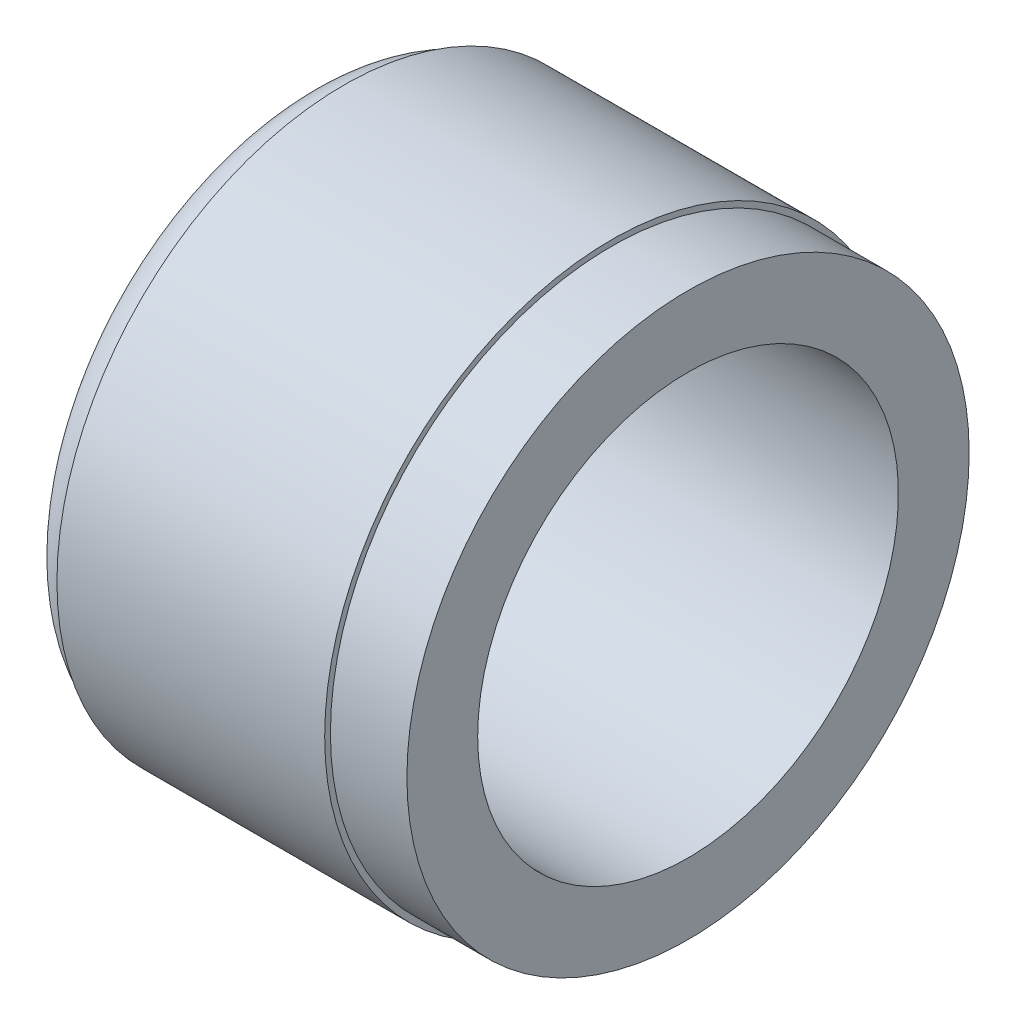
SolidWorks part; units mm, degrees
material "ABS"
ref_plane "Спереди" through (0, 0, 0) normal (0, 0, 1) x (1, 0, 0)
ref_plane "Сверху" through (0, 0, 0) normal (0, 1, 0) x (1, 0, 0)
ref_plane "Справа" through (0, 0, 0) normal (1, 0, 0) x (0, 0, -1)
sketch "Эскиз1" plane through (0, 0, 0) normal (0, 0, 1) x (1, 0, 0)
  line L0 (0, 0) -> (88.0157, 0) construction
  line L1 (0, 11) -> (20, 11)
  line L2 (20, 11) -> (20, 14.7)
  line L3 (20, 14.7) -> (16, 14.7)
  line L4 (16, 14.7) -> (16, 15)
  line L5 (16, 15) -> (2, 15)
  line L6 (2, 15) -> (2, 14.7)
  line L7 (2, 14.7) -> (0, 14.7)
  line L8 (0, 11) -> (0, 14.7)
  dimension "D1" = 20
  dimension "D2" = 30
  dimension "D3" = 4
  dimension "D4" = 2
  dimension "D5" = 0.3
  dimension "D6" = 22
revolve "Повернуть1" add sketch "Эскиз1" angle 360 about L0
fillet "Скругление1" radius 2 1 edges at (0, 0, 14.7)
